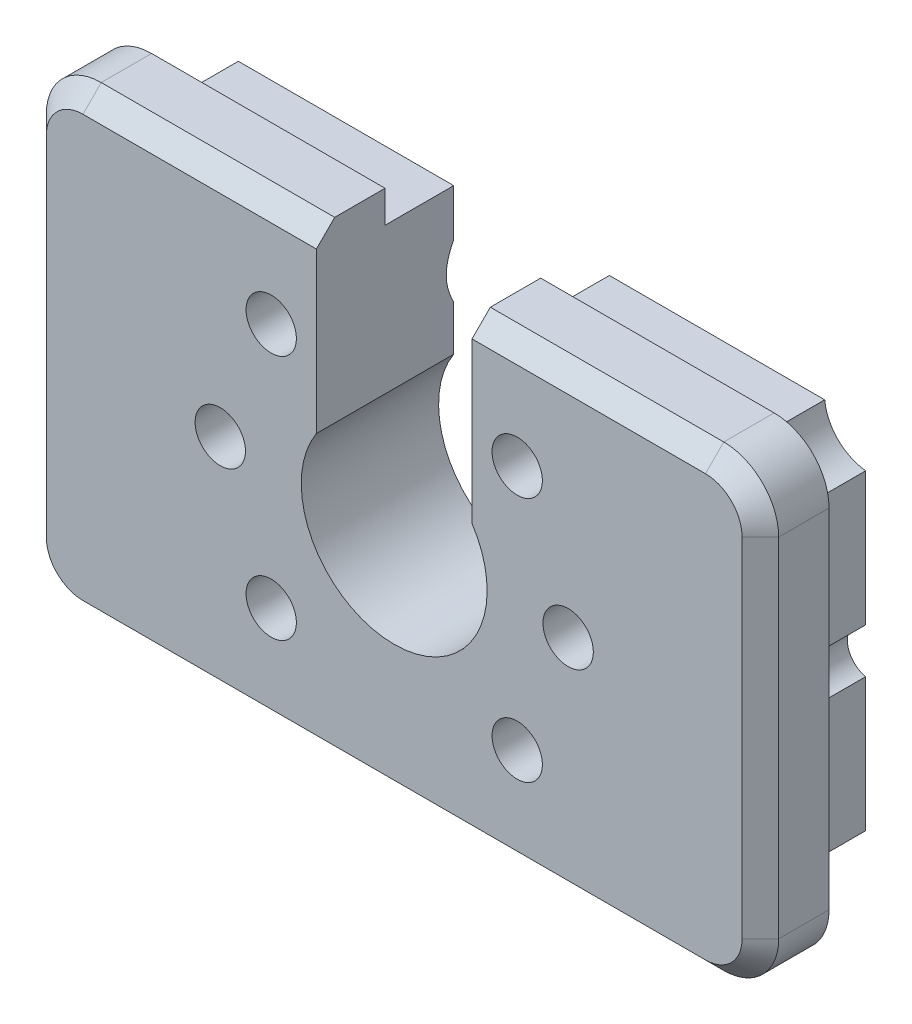
SolidWorks part; units mm, degrees
material "PET"
ref_plane "Front Plane" through (0, 0, 0) normal (0, 0, 1) x (1, 0, 0)
ref_plane "Top Plane" through (0, 0, 0) normal (0, 1, 0) x (1, 0, 0)
ref_plane "Right Plane" through (0, 0, 0) normal (1, 0, 0) x (0, 0, -1)
sketch "Sketch1" plane through (0, 0, 0) normal (0, 0, 1) x (1, 0, 0)
  line L1 (40, -25) -> (-40, -25)
  line L2 (40, -25) -> (40, 25)
  line L3 (40, 25) -> (-40, 25)
  line L4 (-40, -25) -> (-40, 25)
  line L5 (40, -25) -> (-40, 25) construction
  line L6 (40, 25) -> (-40, -25) construction
  point P0 (0, 0)
  dimension "D1" = 50
  dimension "D2" = 80
extrude "Boss-Extrude1" add sketch "Sketch1" against normal blind 7.5
sketch "Sketch2" plane through (0, 0, -7.5) normal (0, 0, -1) x (-1, 0, 0)
  line L8 (36.5, -21.5) -> (36.5, 21.5)
  line L9 (36.5, 21.5) -> (-36.5, 21.5)
  line L10 (-36.5, 21.5) -> (-36.5, -21.5)
  line L11 (-36.5, -21.5) -> (36.5, -21.5)
  line L12 (36.5, -21.5) -> (36.5, 21.5)
  line L13 (36.5, 21.5) -> (-36.5, 21.5)
  line L14 (-36.5, 21.5) -> (-36.5, -21.5)
  line L15 (-36.5, -21.5) -> (36.5, -21.5)
  dimension "D1" = 3.5
extrude "Boss-Extrude2" add sketch "Sketch2" along normal blind 7.5
sketch "Sketch3" plane through (0, 0, 0) normal (0, 0, 1) x (1, 0, 0)
  line L0 (0, 0) -> (0, 51.1675) construction
  line L1 (40, 25) -> (-40, 25) construction
  line L2 (8.5, 5.5473) -> (-8.5, 5.5473) construction
  line L3 (8.5, 5.5473) -> (8.5, 25)
  line L4 (8.5, 25) -> (-8.5, 25)
  line L5 (-8.5, 5.5473) -> (-8.5, 25)
  line L6 (8.5, 5.5473) -> (-8.5, 25) construction
  line L7 (8.5, 25) -> (-8.5, 5.5473) construction
  line L8 (0, 0) -> (-19, 0) construction
  arc A0 (-8.5, 5.5473) -> (8.5, 5.5473) centre (0, 0) ccw
  circle A1 centre (-19, 0) radius 2.75
  circle A2 centre (-13.435, 13.435) radius 2.75
  circle A3 centre (0, 19) radius 2.75 construction
  circle A4 centre (13.435, 13.435) radius 2.75
  circle A5 centre (19, 0) radius 2.75
  circle A6 centre (13.435, -13.435) radius 2.75
  circle A7 centre (0, -19) radius 2.75 construction
  circle A8 centre (-13.435, -13.435) radius 2.75
  point P3 (0, 15.2736)
  point P28 (0, 0)
  dimension "D4" = 5.5
  dimension "D2" = 17
  dimension "D3" = 19
  dimension "D5" = 8
extrude "Cut-Extrude1" cut sketch "Sketch3" against normal through all
fillet "Fillet1" radius 6 4 edges at (40, -25, -3.75) (-40, -25, -3.75) (-40, 25, -3.75) (40, 25, -3.75)
sketch "Sketch4" plane through (0, 0, -15) normal (0, 0, -1) x (-1, 0, 0)
  line L0 (-37, 22) -> (-37, -22) construction
  line L1 (-40, -19) -> (-40, 19) construction
  line L2 (-34, 25) -> (-8.5, 25) construction
  line L4 (34, -25) -> (-34, -25) construction
  line L5 (-37, -22) -> (0, -22) construction
  line L6 (0, 0) -> (0, -22) construction
  circle A0 centre (-37, 22) radius 5
  circle A1 centre (-37, -22) radius 5
  circle A2 centre (-37, 0) radius 2.5
  circle A3 centre (0, -22) radius 2.5
  circle A4 centre (37, -22) radius 5
  circle A5 centre (37, 0) radius 2.5
  circle A6 centre (37, 22) radius 5
  dimension "D4" = 5
  dimension "D5" = 10
  dimension "D1" = 3
  dimension "D2" = 3
  dimension "D3" = 3
extrude "Cut-Extrude2" cut sketch "Sketch4" against normal up to surface (7.5 mm away) up to face at (0, 5.8125, -7.5)
chamfer "Chamfer1" distance 2 angle 45 9 edges at (-21.25, 25, 0) (-38.2426, 23.2426, 0) (-40, 0, 0) (-38.2426, -23.2426, 0) (0, -25, 0) (38.2426, -23.2426, 0) (40, 0, 0) (38.2426, 23.2426, 0) (21.25, 25, 0)
chamfer "Chamfer2" distance 3 angle 45 6 edges at (16.185, -13.435, -15) (-16.25, 0, -15) (-10.685, -13.435, -15) (21.75, 0, -15) (16.185, 13.435, -15) (-10.685, 13.435, -15)
equation "\"hole_radius\"= 10.15mm"
equation "\"D1@Sketch3\"=\"hole_radius\"*2"
equation "\"M5_tap\"=4.2mm       ' Below you can do mesurements as follows: cm, mm, ft, in, m, "
equation "\"M5_clearence\"=5.5mm"
equation "\"M6_tap\"=5mm"
equation "\"M6_clearence\"=6.6mm"
equation "\"work_area_width\"=1100mm"
equation "\"work_area_depth\"=900mm"
equation "\"steel_base_width\"=80mm"
equation "\"steel_base_height\"=50mm"
equation "\"steel_base_wall_thickness\"=3mm"
equation "\"steel_base_radius\"=6mm"
equation "\"steel_sides_width\"=80mm    'this tube is rotated so flip width/height"
equation "\"steel_sides_height\"=50mm    'this tube is rotated so flip width/height"
equation "\"steel_sides_wall_thickness\"=3mm"
equation "\"steel_sides_radius\"=6mm"
equation "\"steel_gantry_width\"=80mm    'this tube is rotated so flip width/height"
equation "\"steel_gantry_height\"=50mm    'this tube is rotated so flip width/height"
equation "\"steel_gantry_wall_thickness\"=3mm"
equation "\"steel_gantry_radius\"=6mm"
equation "\"steel_rollers_width\"=80mm"
equation "\"steel_rollers_height\"=50mm    'keep as low as possible as this increases how big plastic parts are"
equation "\"steel_rollers_wall_thickness\"=3mm"
equation "\"steel_rollers_radius\"=6mm"
equation "\"steel_zbox_width\"=80mm     'if the gantry height (rotated) is too thick, a wider zbox is necessary"
equation "\"steel_zbox_height\"=50mm    'hole patteren changes as the zbox and gantry height (rotated) changes."
equation "\"steel_zbox_wall_thickness\"=3mm"
equation "\"steel_zbox_radius\"=6mm"
equation "\"D2@Sketch1\"=\"steel_rollers_width\""
equation "\"D1@Sketch1\"=\"steel_rollers_height\""
equation "\"D1@Sketch2\"=\"steel_rollers_wall_thickness\" + 0.5mm"
